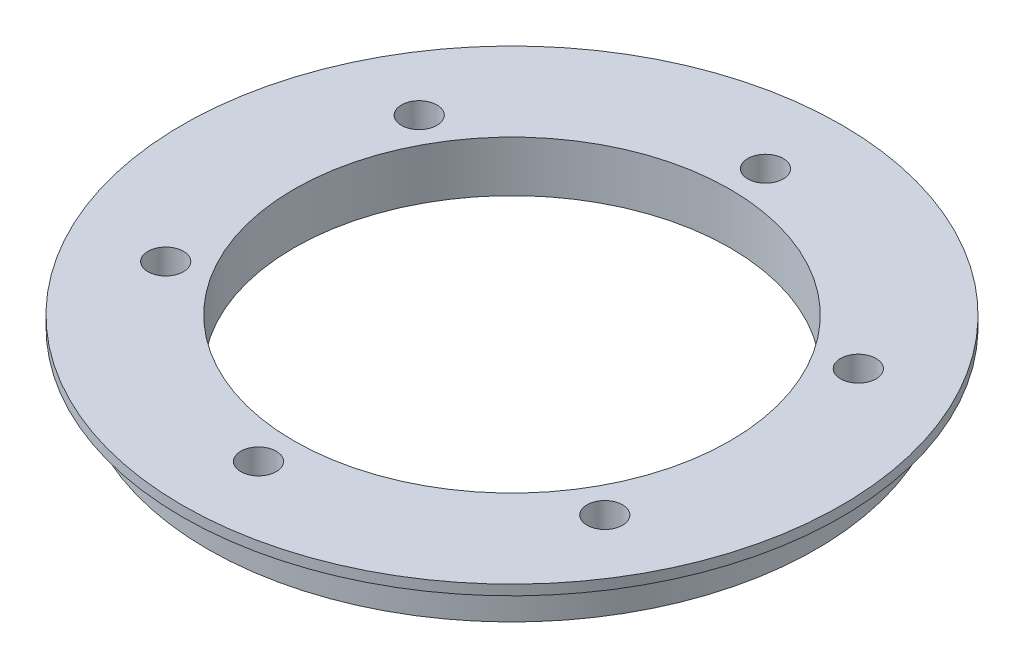
SolidWorks part; units mm, degrees
ref_plane "Front Plane" through (0, 0, 0) normal (0, 0, 1) x (1, 0, 0)
ref_plane "Top Plane" through (0, 0, 0) normal (0, 1, 0) x (1, 0, 0)
ref_plane "Right Plane" through (0, 0, 0) normal (1, 0, 0) x (0, 0, -1)
sketch "Sketch1" plane through (0, 0, 0) normal (0, 1, 0) x (1, 0, 0)
  circle A0 centre (0, 0) radius 30
  circle A2 centre (0, 0) radius 25 construction
  dimension "D1" = 60
  dimension "D2" = 50
extrude "Boss-Extrude1" add sketch "Sketch1" along normal blind 5
sketch "Sketch2" plane through (0, 5, 0) normal (0, 1, 0) x (1, 0, 0)
  circle A0 centre (0, 0) radius 32.5
  dimension "D1" = 65
extrude "Boss-Extrude2" add sketch "Sketch2" against normal blind 1
sketch "Sketch3" plane through (0, 0, 0) normal (0, -1, 0) x (1, 0, 0)
  circle A0 centre (0, 0) radius 21.5
  dimension "D1" = 43
extrude "Cut-Extrude1" cut sketch "Sketch3" against normal blind 25
sketch "Sketch4" plane through (0, 5, 0) normal (0, 1, 0) x (1, 0, 0)
  circle A0 centre (0, 0) radius 25 construction
  circle A1 centre (0, 25) radius 1.75
  circle A2 centre (0, 0) radius 25 construction
  circle A3 centre (21.6506, 12.5) radius 1.75
  circle A4 centre (0, 0) radius 25 construction
  circle A5 centre (21.6506, -12.5) radius 1.75
  circle A6 centre (0, 0) radius 25 construction
  circle A7 centre (0, -25) radius 1.75
  circle A8 centre (0, 0) radius 25 construction
  circle A9 centre (-21.6506, -12.5) radius 1.75
  circle A10 centre (0, 0) radius 25 construction
  circle A11 centre (-21.6506, 12.5) radius 1.75
  point P22 (0, 0)
  dimension "D1" = 50
  dimension "D2" = 3.5
  dimension "D3" = 6
extrude "Cut-Extrude2" cut sketch "Sketch4" against normal blind 25
